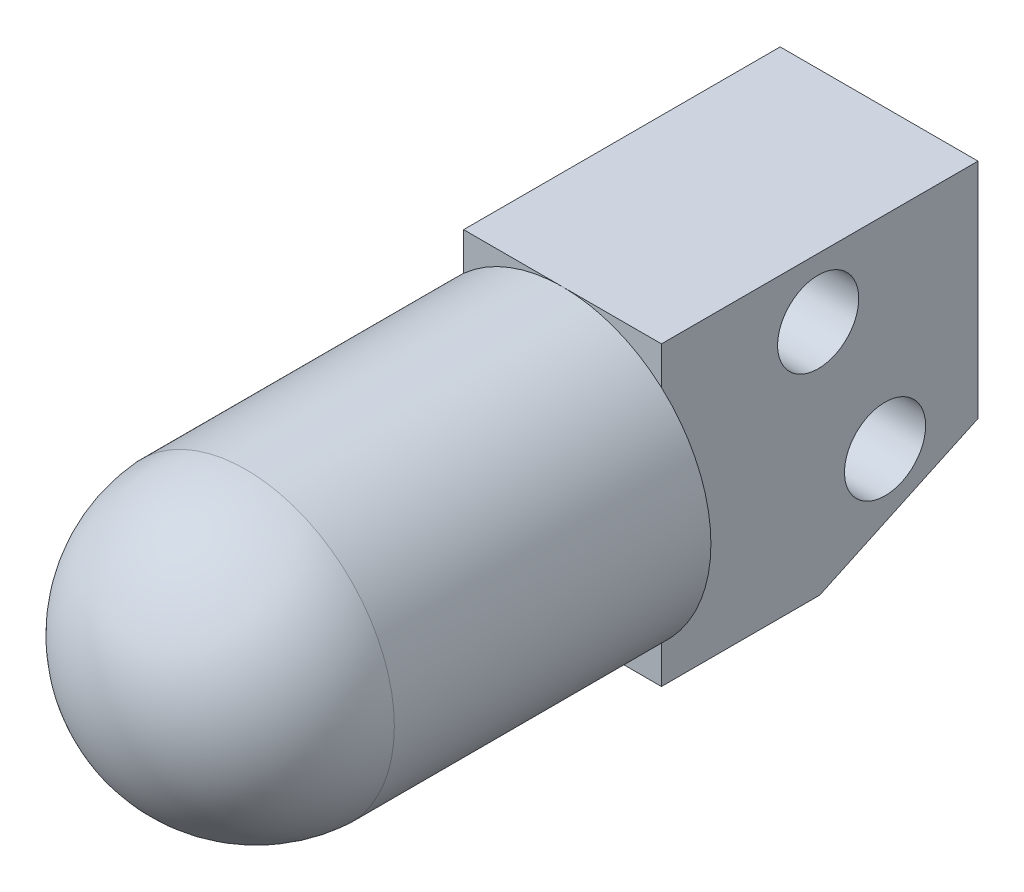
SolidWorks part; units mm, degrees
material "1060 合金"
ref_plane "前视基准面" through (0, 0, 0) normal (0, 0, 1) x (1, 0, 0)
ref_plane "上视基准面" through (0, 0, 0) normal (0, 1, 0) x (1, 0, 0)
ref_plane "右视基准面" through (0, 0, 0) normal (1, 0, 0) x (0, 0, -1)
sketch "草图2" plane through (0, 0, 0) normal (0, 0, 1) x (1, 0, 0)
  circle A0 centre (0, 0) radius 7.5
  dimension "D1" = 15
extrude "凸台-拉伸1" add sketch "草图2" along normal blind 16
dome "圆顶1" faces to dome 1 distance 7 reverse direction no elliptical dome no face at (7.5, 0, 16) parameters "D1"=7
sketch "草图3" plane through (0, 0, 0) normal (0, 0, -1) x (-1, 0, 0)
  line L1 (-5, -7.5) -> (5, -7.5)
  line L2 (-5, -7.5) -> (-5, 7.5)
  line L3 (-5, 7.5) -> (5, 7.5)
  line L4 (5, -7.5) -> (5, 7.5)
  line L5 (-5, -7.5) -> (5, 7.5) construction
  line L6 (-5, 7.5) -> (5, -7.5) construction
  point P0 (0, 0)
  dimension "D1" = 10
  dimension "D2" = 15
extrude "凸台-拉伸2" add sketch "草图3" along normal blind 16
chamfer "倒角1" distance 8 angle 25 1 edges at (0, -7.5, -16) first distance on face at (0, -7.5, -6.4)
sketch "草图4" plane through (0, 0, 0) normal (1, 0, 0) x (0, 0, -1)
  line L0 (1.0054, 7.5) -> (8, -7.5)
  line L1 (16, 7.5) -> (16, -3.7695) construction
  line L2 (16, 7.5) -> (16, -3.7695)
  line L3 (16, 7.5) -> (0, 7.5) construction
  line L4 (16, 7.5) -> (1.0054, 7.5)
  line L5 (8, -7.5) -> (16, -3.7695) construction
  line L6 (8, -7.5) -> (16, -3.7695)
  line L7 (8, -7.5) -> (0, -7.5) construction
  dimension "D1" = 65
hole_wizard "M4 间隙孔1" positions "草图8" profile "草图7" hole size "M4" standard "GB" end condition up to next
sketch "草图8" plane through (5, 0, 0) normal (1, 0, 0) x (0, 0, -1)
  line L0 (11.3021, -2.7505) -> (7.9212, 4.5) construction
  line L2 (1.0054, 7.5) -> (8, -7.5) construction
  line L3 (16, 7.5) -> (0, 7.5) construction
  point P0 (7.9212, 4.5)
  point P2 (11.3021, -2.7505)
  dimension "D1" = 8
  dimension "D2" = 5
  dimension "D3" = 3
sketch "草图7" plane through (5, 4.5, -7.9212) normal (0, 1, 0) x (0, 0, -1)
  line L0 (0, 0) -> (0, 10)
  line L1 (0, 10) -> (2.05, 10)
  line L2 (2.05, 10) -> (2.05, 0)
  line L5 (2.05, 0) -> (0, 0)
  line L11 (0, -6.35) -> (0, 107.95) construction
  dimension "通孔孔直径" = 4.1
  dimension "通孔孔深度" = 10
